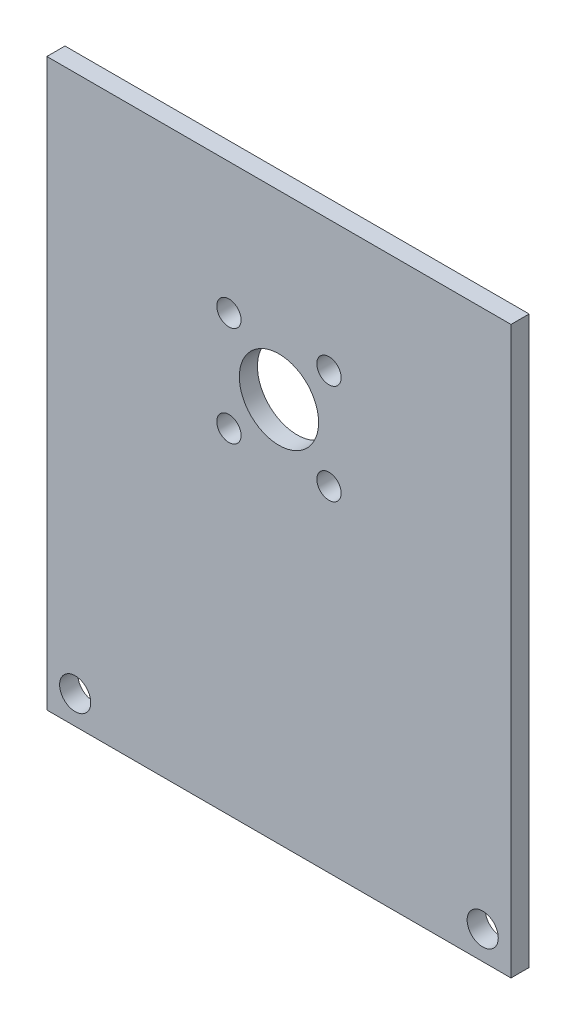
SolidWorks part; units mm, degrees
material "AISI 304"
ref_plane "Front Plane" through (0, 0, 0) normal (0, 0, 1) x (1, 0, 0)
ref_plane "Top Plane" through (0, 0, 0) normal (0, 1, 0) x (1, 0, 0)
ref_plane "Right Plane" through (0, 0, 0) normal (1, 0, 0) x (0, 0, -1)
sketch "Sketch1" plane through (0, 0, 0) normal (0, 0, 1) x (1, 0, 0)
  line L1 (-75, 80) -> (75, 80)
  line L2 (-75, 80) -> (-75, -80)
  line L3 (-75, -80) -> (75, -80)
  line L4 (75, 80) -> (75, -80)
  line L5 (-75, 80) -> (75, -80) construction
  line L6 (-75, -80) -> (75, 80) construction
  point P0 (0, 0)
  dimension "D1" = 150
  dimension "D2" = 160
extrude "Boss-Extrude1" add sketch "Sketch1" along normal blind 3.2
sketch "Sketch2" plane through (0, 0, 3.2) normal (0, 0, 1) x (1, 0, 0)
  line L0 (-75, -80) -> (75, -80) construction
  circle A0 centre (0, -12) radius 7
  circle A1 centre (-36, -75) radius 2.75 construction
  circle A2 centre (36, -75) radius 2.75 construction
  circle A3 centre (-36, -75) radius 2.75
  circle A4 centre (36, -75) radius 2.75
  dimension "D1" = 14
  dimension "D2" = 68
extrude "Cut-Extrude1" cut sketch "Sketch2" against normal up to next
sketch "Sketch3" plane through (0, 0, 3.2) normal (0, 0, 1) x (1, 0, 0)
  line L0 (-83.9315, 71.9315) -> (0, -12) construction
  line L1 (0, -12) -> (-75, -12) construction
  line L2 (-75, 80) -> (-75, -80) construction
  circle A0 centre (-8.8388, -3.1612) radius 2.15
  dimension "D1" = 4.3
  dimension "D2" = 12.5
  dimension "D3" = 45
extrude "Cut-Extrude2" cut sketch "Sketch3" against normal through all
pattern_circular "CirPattern1" count 4 every 90 about axis through (0, -12, 3.2) along (0, 0, 1) of "Cut-Extrude2"
sketch "Sketch5" plane through (0, 0, 3.2) normal (0, 0, 1) x (1, 0, 0)
  line L0 (-75, -80) -> (75, -80) construction
  line L1 (-41, -80) -> (41, -80)
  line L2 (-41, 20) -> (41, 20)
  line L5 (41, -80) -> (41, 20)
  line L7 (-41, 20) -> (-41, -80)
  dimension "D1" = 82
  dimension "D2" = 100
extrude "Cut-Extrude4" cut sketch "Sketch5" against normal blind 10 flip side to cut
sketch "Sketch6" plane through (0, 0, 3.2) normal (0, 0, 1) x (1, 0, 0)
  line L0 (0, -12) -> (0, 29) construction
